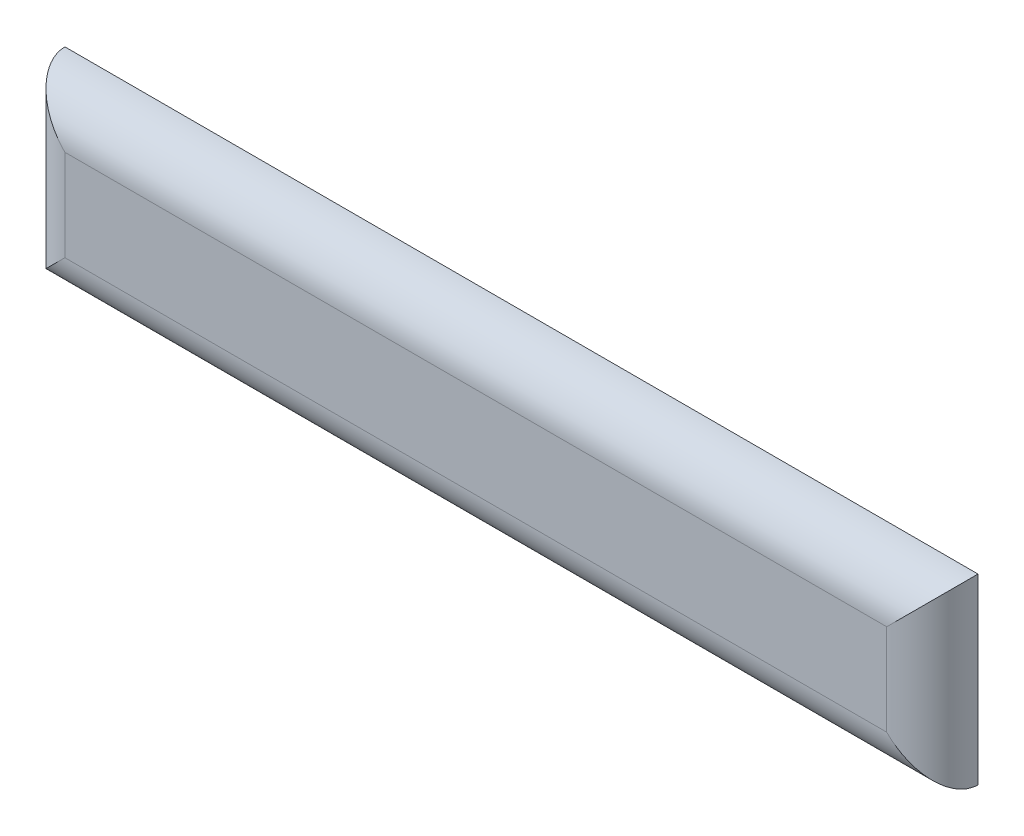
SolidWorks part; units mm, degrees
ref_plane "Front Plane" through (0, 0, 0) normal (0, 0, 1) x (1, 0, 0)
ref_plane "Top Plane" through (0, 0, 0) normal (0, 1, 0) x (1, 0, 0)
ref_plane "Right Plane" through (0, 0, 0) normal (1, 0, 0) x (0, 0, -1)
sketch "Sketch1" plane through (0, 0, 0) normal (0, 0, 1) x (1, 0, 0)
  line L1 (-100, 20) -> (100, 20)
  line L2 (-100, 20) -> (-100, -20)
  line L3 (-100, -20) -> (100, -20)
  line L4 (100, 20) -> (100, -20)
  line L5 (-100, 20) -> (100, -20) construction
  line L6 (-100, -20) -> (100, 20) construction
  point P0 (0, 0)
extrude "Boss-Extrude1" add sketch "Sketch1" along normal blind 10
fillet "Fillet1" radius 10 4 edges at (0, 20, 10) (100, 0, 10) (0, -20, 10) (-100, 0, 10)
